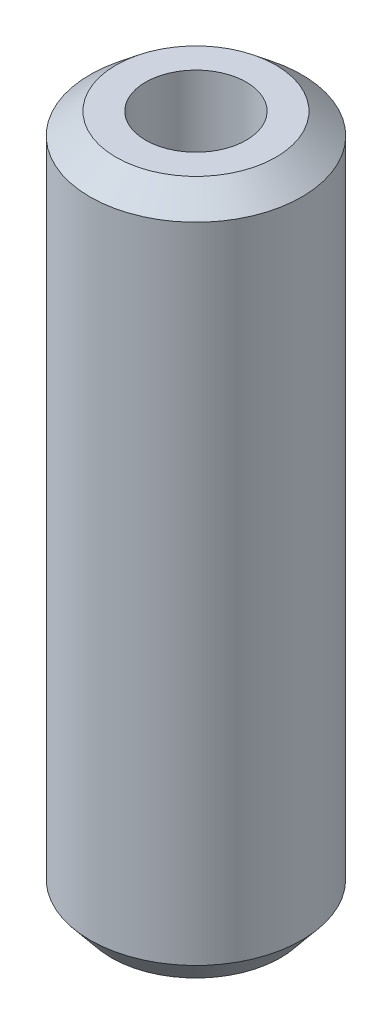
SolidWorks part; units mm, degrees
ref_plane "Front Plane" through (0, 0, 0) normal (0, 0, 1) x (1, 0, 0)
ref_plane "Top Plane" through (0, 0, 0) normal (0, 1, 0) x (1, 0, 0)
ref_plane "Right Plane" through (0, 0, 0) normal (1, 0, 0) x (0, 0, -1)
sketch "Sketch1" plane through (0, 0, 0) normal (0, 1, 0) x (1, 0, 0)
  circle A0 centre (0, 0) radius 22.5
  dimension "SHAFT_OD" = 45
extrude "Boss-Extrude1" add sketch "Sketch1" along normal blind 146.7889
sketch "Sketch2" plane through (0, 0, 0) normal (0, 1, 0) x (1, 0, 0)
  circle A0 centre (0, 0) radius 10.6952
  dimension "BORE_D" = 21.3904
extrude "Cut-Extrude1" cut sketch "Sketch2" along normal through all
chamfer "Chamfer1" distance 4.5355 angle 50.584 2 edges at (0, 146.7889, 22.5) (0, 0, 22.5) first distance on face at (0, 146.7889, 22.5) first distance on face at (0, 0, 10.6952)
